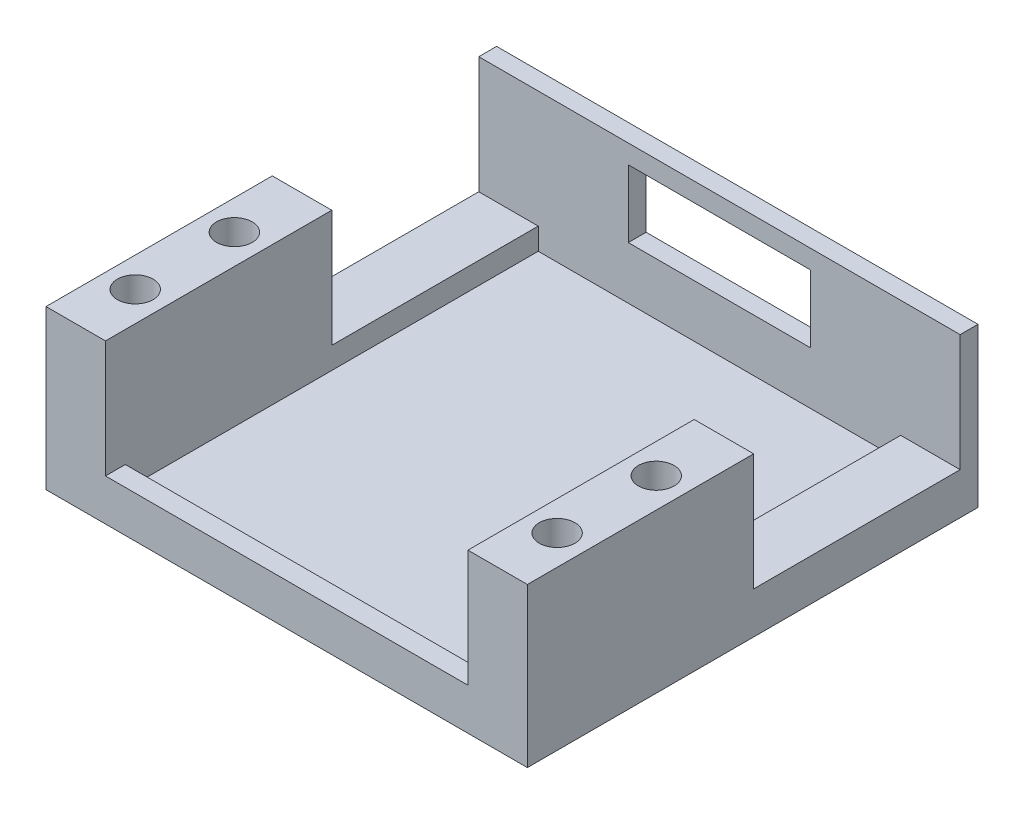
SolidWorks part; units mm, degrees
ref_plane "Front Plane" through (0, 0, 0) normal (0, 0, 1) x (1, 0, 0)
ref_plane "Top Plane" through (0, 0, 0) normal (0, 1, 0) x (1, 0, 0)
ref_plane "Right Plane" through (0, 0, 0) normal (1, 0, 0) x (0, 0, -1)
sketch "Sketch1" plane through (0, 0, 0) normal (0, 1, 0) x (1, 0, 0)
  line L1 (0, 0) -> (18.28, 0)
  line L2 (0, 0) -> (0, 20.828)
  line L3 (0, 20.828) -> (18.28, 20.828)
  line L4 (18.28, 0) -> (18.28, 20.828)
  line L5 (0, 20.828) -> (-3, 20.828)
  line L6 (0, 20.828) -> (0, 0)
  line L7 (0, 0) -> (-3, 0)
  line L8 (-3, 20.828) -> (-3, 0)
  line L9 (18.28, 0) -> (21.28, 0)
  line L10 (18.28, 0) -> (18.28, 20.828)
  line L11 (18.28, 20.828) -> (21.28, 20.828)
  line L12 (21.28, 0) -> (21.28, 20.828)
  line L13 (-3, 0) -> (21.28, 0)
  line L14 (-3, 0) -> (-3, -1)
  line L15 (-3, -1) -> (21.28, -1)
  line L16 (21.28, 0) -> (21.28, -1)
  line L17 (-3, 20.828) -> (21.28, 20.828)
  line L18 (-3, 20.828) -> (-3, 21.728)
  line L19 (-3, 21.728) -> (21.28, 21.728)
  line L20 (21.28, 20.828) -> (21.28, 21.728)
  point P17 (0, 0)
  dimension "D1" = 20.828
  dimension "D2" = 18.28
  dimension "D3" = 3
  dimension "D4" = 3
  dimension "D5" = 1
  dimension "D7" = 0.9
extrude "USB Lip" add sketch "Sketch1" along normal blind 1.55 contours L11 L20 L19 L18 L5 L3 region at (9.14, 0, -21.278)
extrude "Base w/ 1.1mm component offset" add sketch "Sketch1<3>" against normal blind 1 from offset 1.1 separate body contours L1 L4 L3 L2 region at (9.14, 0, -10.414) offset against normal yes
sketch "Sketch1<3>" plane through (0, 0, 0) normal (0, 1, 0) x (1, 0, 0) same geometry as "Sketch1"
extrude "Sides" add sketch "Sketch1<4>" against normal up to surface (2.1 mm away) contours L5 L8 L7 L2 | L16 L9 L1 L7 L14 L15 | L9 L12 L11 L4 | L11 L20 L19 L18 L5 L3 region at (-1.5, 0, -10.414) region at (9.14, 0, 0.5) region at (19.78, 0, -10.414) region at (9.14, 0, -21.278) up to face at (9.14, -2.1, -10.414)
sketch "Sketch1<4>" plane through (0, 0, 0) normal (0, 1, 0) x (1, 0, 0) same geometry as "Sketch1"
sketch "Sketch2" plane through (0, 1.55, 0) normal (0, 1, 0) x (1, 0, 0)
  line L0 (9.14, 21.728) -> (9.14, 20.828) construction
  line L1 (-3, 21.728) -> (21.28, 21.728) construction
  line L2 (-3, 20.828) -> (21.28, 20.828) construction
  line L3 (13.74, 21.728) -> (13.74, 20.828)
  line L4 (-3, 21.728) -> (4.54, 21.728)
  line L5 (-3, 21.728) -> (-3, 20.828)
  line L6 (-3, 20.828) -> (4.54, 20.828)
  line L7 (4.54, 21.728) -> (4.54, 20.828)
  line L8 (21.28, 20.828) -> (13.74, 20.828)
  line L9 (21.28, 21.728) -> (21.28, 20.828)
  line L10 (21.28, 21.728) -> (13.74, 21.728)
  line M3 (-3, 20.828) -> (21.28, 20.828)
  line M4 (21.28, 20.828) -> (21.28, 21.728)
  line M5 (21.28, 21.728) -> (-3, 21.728)
  line M6 (-3, 21.728) -> (-3, 20.828)
  dimension "D1" = 0.9
  dimension "D2" = 4.6
extrude "USB Sides" add sketch "Sketch2" along normal blind 3.4 contours L7 M5 M6 M3 | L3 M5 M3 M4 region at (17.51, 1.55, -21.278) region at (0.77, 1.55, -21.278)
sketch "Sketch3" plane through (0, 4.95, 0) normal (0, 1, 0) x (1, 0, 0)
  line L1 (-3, 20.828) -> (21.28, 20.828)
  line L2 (-3, 20.828) -> (-3, 21.728)
  line L3 (-3, 21.728) -> (21.28, 21.728)
  line L4 (21.28, 20.828) -> (21.28, 21.728)
extrude "USB Top" add sketch "Sketch3" along normal blind 0.95
sketch "Sketch4" plane through (0, 0, 0) normal (0, 1, 0) x (1, 0, 0)
  line L0 (0, 10.414) -> (-3, 10.414) construction
  line L1 (0, 0) -> (0, 20.828) construction
  line L2 (-3, 20.828) -> (-3, -1) construction
  line L3 (-3, -1) -> (21.28, -1) construction
  line L4 (-3, 10.414) -> (0, 10.414)
  line L5 (-3, 10.414) -> (-3, -1)
  line L6 (-3, -1) -> (0, -1)
  line L7 (0, 10.414) -> (0, -1)
  line L8 (9.14, 0) -> (9.14, -1) construction
  line L9 (0, 0) -> (18.28, 0) construction
  line L10 (18.28, 10.414) -> (18.28, -1)
  line L11 (21.28, -1) -> (18.28, -1)
  line L12 (21.28, 10.414) -> (21.28, -1)
  line L13 (21.28, 10.414) -> (18.28, 10.414)
  dimension "D1" = 11.414
  dimension "D2" = 3
extrude "Side Guards" add sketch "Sketch4" along normal up to surface (5.9 mm away) up to face at (9.14, 5.9, -21.278)
sketch "Sketch5" plane through (0, 5.9, 0) normal (0, 1, 0) x (1, 0, 0)
  line L0 (-3, 10.414) -> (0, 10.414) construction
  line L1 (-1.5, 10.414) -> (-1.5, -1) construction
  line L2 (0, -1) -> (-3, -1) construction
  line L3 (19.78, 10.414) -> (19.78, -1) construction
  line L4 (18.28, 10.414) -> (21.28, 10.414) construction
  line L5 (21.28, -1) -> (18.28, -1) construction
  circle A0 centre (-1.5, 2) radius 0.9
  circle A1 centre (19.78, 2) radius 0.9
  circle A2 centre (-1.5, 7) radius 0.9
  circle A3 centre (19.78, 7) radius 0.9
  point P20 (0, 0)
  dimension "D1" = 1.8
  dimension "D2" = 1.8
  dimension "D4" = 1.8
  dimension "D5" = 1.8
  dimension "D3" = 3
  dimension "D6" = 5
extrude "Mount Holes" cut sketch "Sketch5" against normal through all
